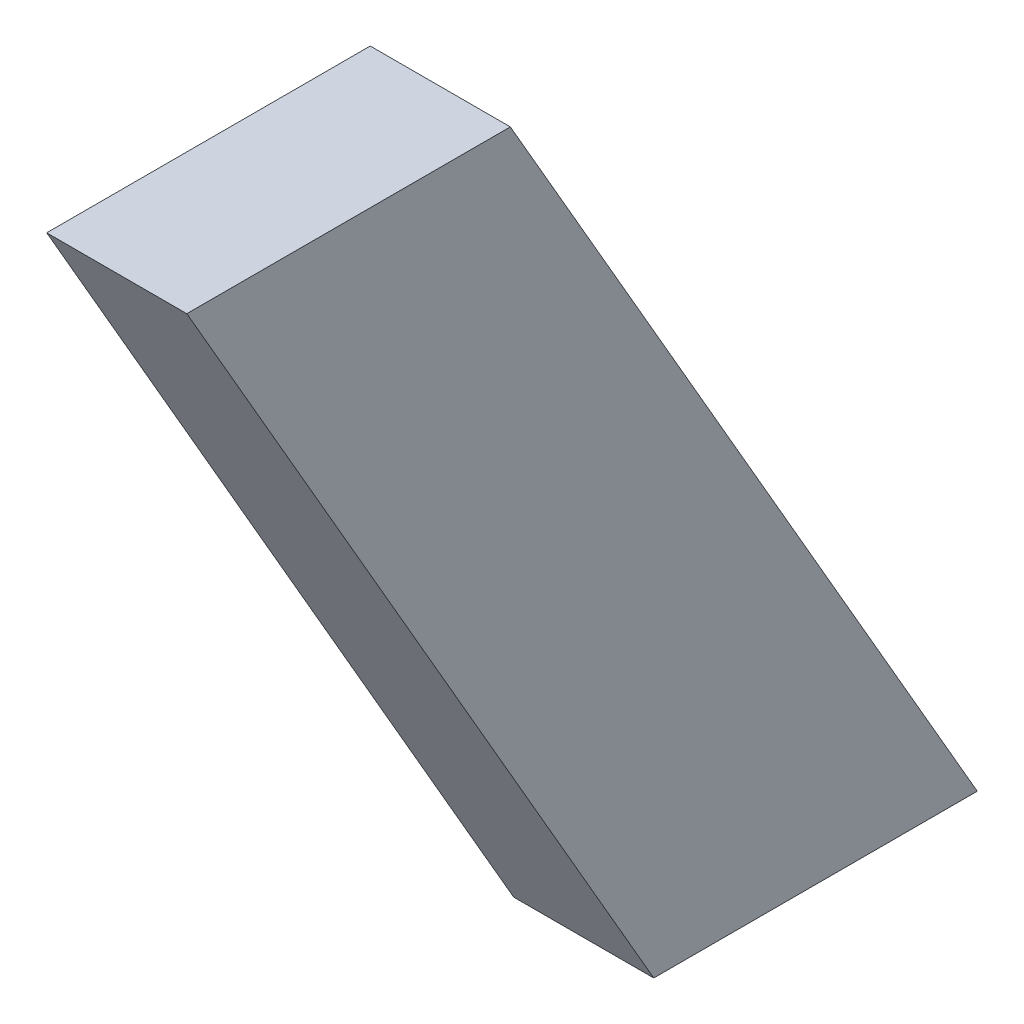
SolidWorks part; units mm, degrees
ref_plane "Front Plane" through (0, 0, 0) normal (0, 0, 1) x (1, 0, 0)
ref_plane "Top Plane" through (0, 0, 0) normal (0, 1, 0) x (1, 0, 0)
ref_plane "Right Plane" through (0, 0, 0) normal (1, 0, 0) x (0, 0, -1)
sketch "Sketch2" plane through (0, 0, 0) normal (1, 0, 0) x (0, 0, -1)
  line L0 (0, 0) -> (43.9941, 0)
  line L1 (43.9941, 0) -> (107.4941, -109.9852)
  line L2 (107.4941, -109.9852) -> (63.5, -109.9852)
  line L3 (63.5, -109.9852) -> (0, 0)
  dimension "D1" = 60
  dimension "D2" = 38.1
  dimension "D3" = 127
extrude "Boss-Extrude1" add sketch "Sketch2" along normal blind 19.05
